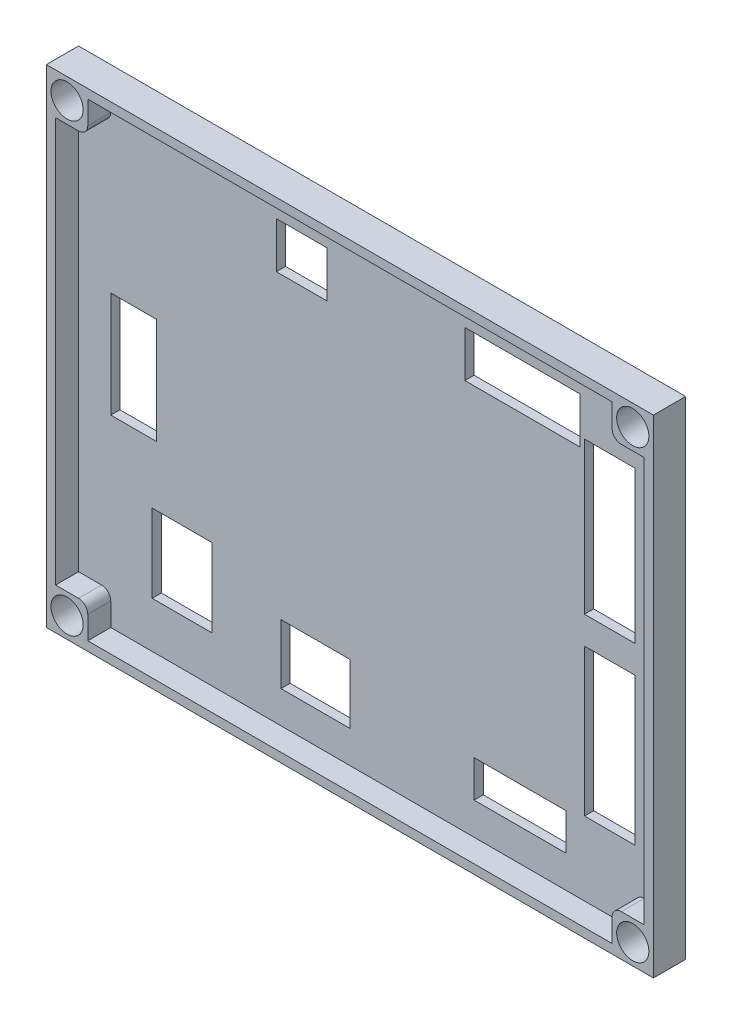
SolidWorks part; units mm, degrees
ref_plane "Plan de face" through (0, 0, 0) normal (0, 0, 1) x (1, 0, 0)
ref_plane "Plan de dessus" through (0, 0, 0) normal (0, 1, 0) x (1, 0, 0)
ref_plane "Plan de droite" through (0, 0, 0) normal (1, 0, 0) x (0, 0, -1)
sketch "Esquisse1" plane through (0, 0, 0) normal (0, 0, 1) x (1, 0, 0)
  line L0 (123, 0) -> (132, 0)
  line L1 (0, 0) -> (132, 0)
  line L2 (0, 0) -> (0, 106)
  line L3 (0, 106) -> (132, 106)
  line L4 (132, 0) -> (132, 106)
  line L5 (2, 104) -> (130, 104)
  line L6 (2, 104) -> (2, 2)
  line L7 (2, 2) -> (130, 2)
  line L8 (130, 104) -> (130, 2)
  line L9 (0, 0) -> (9, 0)
  line L10 (0, 0) -> (0, 9)
  line L11 (0, 9) -> (9, 9)
  line L12 (9, 0) -> (9, 9)
  line L13 (123, 0) -> (123, 9)
  line L14 (123, 9) -> (132, 9)
  line L15 (132, 0) -> (132, 9)
  line L16 (123, 97) -> (132, 97)
  line L17 (123, 97) -> (123, 106)
  line L18 (123, 106) -> (132, 106)
  line L19 (132, 97) -> (132, 106)
  line L20 (0, 97) -> (9, 97)
  line L21 (0, 97) -> (0, 106)
  line L22 (0, 106) -> (9, 106)
  line L23 (9, 97) -> (9, 106)
  circle A0 centre (4.5, 4.5) radius 3.5
  circle A1 centre (127.5, 4.5) radius 3.5
  circle A2 centre (127.5, 101.5) radius 3.5
  circle A3 centre (4.5, 101.5) radius 3.5
  dimension "D11" = 7
  dimension "D12" = 7
  dimension "D13" = 7
  dimension "D14" = 7
  dimension "D1" = 132
  dimension "D2" = 106
  dimension "D3" = 2
  dimension "D4" = 2
  dimension "D5" = 2
  dimension "D6" = 2
  dimension "D7" = 9
  dimension "D8" = 9
  dimension "D9" = 4.5
  dimension "D10" = 4.5
extrude "Boss.-Extru.1" add sketch "Esquisse1" along normal blind 2 contours L23 L20 L6 L11 L12 L7 L13 L14 L8 L16 L17 L5 region at (66, 53, 0)
extrude "Boss.-Extru.2" add sketch "Esquisse1<3>" along normal blind 7 contours L23 L5 L17 L3 | A3 L5 L23 L3 L2 L20 L6 | L5 A3 | L6 A3 | L5 A3 L6 | A3 L6 L20 L23 L5 | L20 L2 L11 L6 | A0 L6 L11 L2 L1 L12 L7 | A0 L7 L12 L11 L6 | L6 A0 L7 | L6 A0 | L7 A0 | L1 L13 L7 L12 | A0 L6 L7 | A3 L5 L6 | A1 L8 L14 L13 L7 | A1 L7 L13 L0 L4 L14 L8 | L8 A1 | L8 A1 L7 | L7 A1 | A1 L7 L8 | L16 L8 L14 L4 | A2 L5 L8 L16 L4 L3 L17 | A2 L5 L17 L16 L8 | L8 A2 L5 | L5 A2 | L8 A2 | A2 L8 L5 region at (123.1273, 1, 0) region at (66, 1, 0) region at (4.5, 0.1273, 0) region at (123.099, 5.5, 0) region at (131, 53, 0) region at (7.9747, 2.099, 0) region at (127.1913, 4.8087, 0) region at (127.5, 1.5947, 0) region at (131, 97.1273, 0) region at (1, 53, 0) region at (4.5, 1.5947, 0) region at (4.8087, 4.8087, 0) region at (129.9832, 2.0168, 0) region at (130.4053, 4.5, 0) region at (126.5, 97.099, 0) region at (0.1273, 101.5, 0) region at (2.0168, 2.0168, 0) region at (66, 105, 0) region at (127.1913, 101.1913, 0) region at (130.4053, 101.5, 0) region at (2.099, 98.0253, 0) region at (1.5947, 4.5, 0) region at (129.9832, 103.9832, 0) region at (127.5, 104.4053, 0) region at (1.5947, 101.5, 0) region at (4.8087, 101.1913, 0) region at (2.0168, 103.9832, 0) region at (4.5, 104.4053, 0)
sketch "Esquisse1<3>" plane through (0, 0, 0) normal (0, 0, 1) x (1, 0, 0) same geometry as "Esquisse1"
extrude "Enlèv. mat.-Extru.1" cut sketch "Esquisse1<4>" against normal blind 5 from offset 7 contours L6 A3 | L5 A3 | L5 A3 L6 | L6 A0 | L6 A0 L7 | L7 A0 | L8 A1 L7 | L8 A1 | L7 A1 | L5 A2 | L8 A2 L5 | L8 A2 region at (127.1913, 4.8087, 0) region at (127.5, 1.5947, 0) region at (4.5, 1.5947, 0) region at (4.8087, 4.8087, 0) region at (130.4053, 4.5, 0) region at (127.1913, 101.1913, 0) region at (130.4053, 101.5, 0) region at (1.5947, 4.5, 0) region at (127.5, 104.4053, 0) region at (1.5947, 101.5, 0) region at (4.8087, 101.1913, 0) region at (4.5, 104.4053, 0)
sketch "Esquisse1<4>" plane through (0, 0, 0) normal (0, 0, 1) x (1, 0, 0) same geometry as "Esquisse1"
fillet "Congé2" radius 2 4 edges at (123, 9, 4.5) (9, 9, 4.5) (123, 97, 4.5) (9, 97, 4.5)
sketch "Esquisse2" plane through (0, 0, 0) normal (0, 0, -1) x (-1, 0, 0)
  line L0 (-112, 69) -> (-112, 66)
  line L1 (-132, 106) -> (0, 106)
  line L2 (-132, 106) -> (-132, 0)
  line L3 (-132, 0) -> (0, 0)
  line L4 (0, 106) -> (0, 0)
  line L5 (-123, 97) -> (-9, 97)
  line L6 (-123, 97) -> (-123, 9)
  line L7 (-123, 9) -> (-9, 9)
  line L8 (-9, 97) -> (-9, 9)
  line L9 (-123, 89) -> (-112, 89)
  line L10 (-123, 89) -> (-123, 69)
  line L12 (-112, 89) -> (-112, 69)
  line L14 (-123, 66) -> (-123, 56)
  line L15 (-123, 56) -> (-112, 56)
  line L16 (-112, 66) -> (-112, 56)
  line L17 (-123, 50) -> (-112, 50)
  line L18 (-123, 50) -> (-123, 38.8534)
  line L19 (-123, 38.8534) -> (-112, 38.8534)
  line L20 (-112, 50) -> (-112, 38.8534)
  line L21 (-123, 27.9428) -> (-112, 27.9428)
  line L22 (-123, 27.9428) -> (-123, 18)
  line L23 (-123, 18) -> (-112, 18)
  line L24 (-112, 27.9428) -> (-112, 18)
  line L25 (-108, 9) -> (-88, 9)
  line L26 (-108, 9) -> (-108, 17)
  line L27 (-108, 17) -> (-88, 17)
  line L28 (-88, 9) -> (-88, 17)
  line L29 (-61, 9) -> (-46, 9)
  line L30 (-61, 9) -> (-61, 22)
  line L31 (-61, 22) -> (-46, 22)
  line L32 (-46, 9) -> (-46, 22)
  line L38 (-9, 32.57) -> (-9, 46.1934)
  line L41 (-9, 42) -> (-19, 42)
  line L42 (-9, 42) -> (-9, 65)
  line L43 (-9, 65) -> (-19, 65)
  line L44 (-19, 42) -> (-19, 65)
  line L45 (-31, 29) -> (-18, 29)
  line L46 (-31, 29) -> (-31, 12)
  line L47 (-31, 12) -> (-18, 12)
  line L48 (-18, 29) -> (-18, 12)
  line L49 (-45, 97) -> (-56, 97)
  line L50 (-45, 97) -> (-45, 87)
  line L51 (-45, 87) -> (-56, 87)
  line L52 (-56, 97) -> (-56, 87)
  line L53 (-86, 97) -> (-111, 97)
  line L54 (-86, 97) -> (-86, 87)
  line L55 (-86, 87) -> (-111, 87)
  line L56 (-111, 97) -> (-111, 87)
  line L57 (-112, 27.9428) -> (-112, 38.8534)
  point P34 (-86, 92)
  dimension "D1" = 114
  dimension "D2" = 88
  dimension "D3" = 9
  dimension "D4" = 9
  dimension "D5" = 8
  dimension "D6" = 11
  dimension "D7" = 11
  dimension "D8" = 41
  dimension "D9" = 11
  dimension "D10" = 47
  dimension "D11" = 79
  dimension "D12" = 15
  dimension "D13" = 35
  dimension "D14" = 8
  dimension "D15" = 62
  dimension "D16" = 77
  dimension "D17" = 13
  dimension "D18" = 92
  dimension "D19" = 105
  dimension "D20" = 3
  dimension "D21" = 20
  dimension "D22" = 32
  dimension "D23" = 55
  dimension "D24" = 10
  dimension "D25" = 12
  dimension "D26" = 37
  dimension "D27" = 10
  dimension "D28" = 67
  dimension "D29" = 78
  dimension "D30" = 10
extrude "Enlèv. mat.-Extru.2" cut sketch "Esquisse2" against normal through all contours L5 L56 L55 L54 | L16 L0 L12 L9 L6 L15 | L20 L17 L6 L19 | L21 L57 L19 L6 | L24 L21 L6 L23 | L7 L28 L27 L26 | L7 L32 L31 L30 | L48 L45 L46 L47 | L44 L41 L8 L43 | L5 L52 L51 L50 region at (117.5, 72.5, 0) region at (117.5, 44.4267, 0) region at (98.5, 92, 0) region at (117.5, 33.3981, 0) region at (117.5, 22.9714, 0) region at (50.5, 92, 0) region at (98, 13, 0) region at (14, 53.5, 0) region at (53.5, 15.5, 0) region at (24.5, 20.5, 0)
sketch "Esquisse3" plane through (0, 0, 0) normal (0, 0, -1) x (-1, 0, 0)
  text T0 "MSC" font "Century Gothic" height in points 72
extrude "Enlèv. mat.-Extru.3" cut sketch "Esquisse3" against normal blind 1
